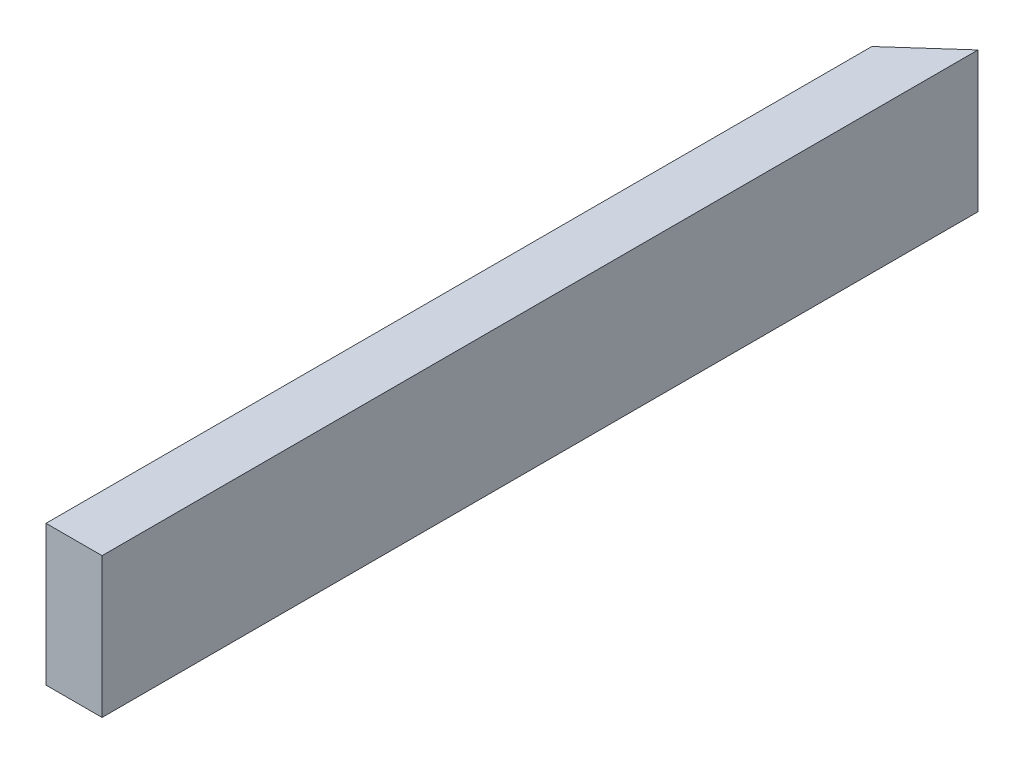
SolidWorks part; units mm, degrees
ref_plane "Front Plane" through (0, 0, 0) normal (0, 0, 1) x (1, 0, 0)
ref_plane "Top Plane" through (0, 0, 0) normal (0, 1, 0) x (1, 0, 0)
ref_plane "Right Plane" through (0, 0, 0) normal (1, 0, 0) x (0, 0, -1)
sketch "Sketch1" plane through (0, 0, 0) normal (0, 0, 1) x (1, 0, 0)
  line L1 (-4.1032, 12.8387) -> (-0.9032, 12.8387)
  line L2 (-4.1032, 12.8387) -> (-4.1032, 4.8387)
  line L3 (-4.1032, 4.8387) -> (-0.9032, 4.8387)
  line L4 (-0.9032, 12.8387) -> (-0.9032, 4.8387)
  dimension "D1" = 3.2
  dimension "D2" = 8
extrude "Boss-Extrude1" add sketch "Sketch1" along normal blind 50
ref_plane "Plane1" through (0, 12.8387, 0) normal (0, 1, 0) x (1, 0, 0)
sketch "Sketch3" plane through (0, 12.8387, 0) normal (0, 1, 0) x (1, 0, 0)
  line L0 (-0.9032, 0) -> (-4.1032, -2.8611)
  line L1 (-4.1032, -50) -> (-4.1032, 0) construction
  line L2 (-4.1032, -2.8611) -> (-4.1032, 0)
  line L3 (-4.1032, 0) -> (-0.9032, 0)
  dimension "D1" = 41.8
extrude "Cut-Extrude1" cut sketch "Sketch3" against normal blind 52
